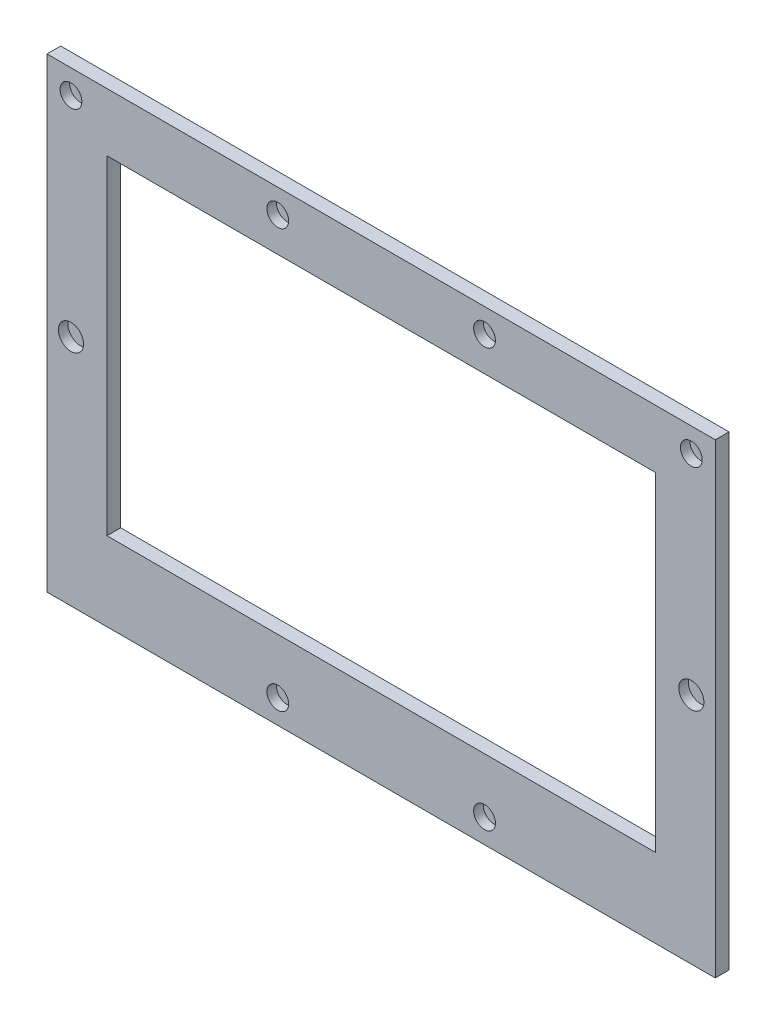
SolidWorks part; units mm, degrees
ref_plane "Front Plane" through (0, 0, 0) normal (0, 0, 1) x (1, 0, 0)
ref_plane "Top Plane" through (0, 0, 0) normal (0, 1, 0) x (1, 0, 0)
ref_plane "Right Plane" through (0, 0, 0) normal (1, 0, 0) x (0, 0, -1)
sketch "Sketch1" plane through (0, 0, 0) normal (0, 0, 1) x (1, 0, 0)
  line L1 (85.5, -56) -> (-85.5, -56)
  line L2 (85.5, -56) -> (85.5, 56)
  line L3 (85.5, 56) -> (-85.5, 56)
  line L4 (-85.5, -56) -> (-85.5, 56)
  line L5 (85.5, -56) -> (-85.5, 56) construction
  line L6 (85.5, 56) -> (-85.5, -56) construction
  line L11 (80, -45) -> (-80, -45)
  line L12 (80, -45) -> (80, 51)
  line L13 (80, 51) -> (-80, 51)
  line L14 (-80, -45) -> (-80, 51)
  line L15 (80, -45) -> (-80, 51) construction
  line L16 (80, 51) -> (-80, -45) construction
  line L17 (-14.5, -56) -> (14.5, -56)
  line L18 (-14.5, -56) -> (-14.5, -59)
  line L19 (-14.5, -59) -> (14.5, -59)
  line L20 (14.5, -56) -> (14.5, -59)
  line L21 (97.5, 68) -> (-97.5, 68)
  line L22 (97.5, 68) -> (97.5, -68)
  line L23 (97.5, -68) -> (-97.5, -68)
  line L24 (-97.5, 68) -> (-97.5, -68)
  line L25 (97.5, 68) -> (-97.5, -68) construction
  line L26 (97.5, -68) -> (-97.5, 68) construction
  point P0 (0, 0)
  point P6 (0, 0)
  point P7 (0, 3)
  point P16 (0, 0)
  dimension "D1" = 171
  dimension "D2" = 112
  dimension "D3" = 96
  dimension "D4" = 160
  dimension "D5" = 5
  dimension "D6" = 71
  dimension "D7" = 29
  dimension "D8" = 3
  dimension "D9" = 12
  dimension "D10" = 17.5
  dimension "D11" = 12
extrude "Boss-Extrude1" add sketch "Sketch1" against normal blind 2 contours L4 L1 L2 L3 L11 L14 L13 L12 | L21 L24 L23 L22 L1 L20 L19 L18 L4 L3 L2 | L20 L1 L18 L19 region at (50, -53.9559, 0) region at (0, -57.5, 0) region at (95.1226, 0, 0)
extrude "Boss-Extrude2" add sketch "Sketch1<3>" along normal blind 2 contours L21 L24 L23 L22 L1 L20 L19 L18 L4 L3 L2 | L4 L1 L2 L3 L11 L14 L13 L12 | L20 L1 L18 L19 region at (50, -53.9559, 0) region at (0, -57.5, 0) region at (95.1226, 0, 0)
sketch "Sketch1<3>" plane through (0, 0, 0) normal (0, 0, 1) x (1, 0, 0) same geometry as "Sketch1"
sketch "Sketch2" plane through (0, 0, 2) normal (0, 0, 1) x (1, 0, 0)
  line L0 (97.5, 68) -> (-97.5, 68) construction
  line L1 (90.5, -61) -> (-90.5, -61) construction
  line L2 (90.5, -61) -> (90.5, 61) construction
  line L3 (90.5, 61) -> (-90.5, 61) construction
  line L4 (-90.5, -61) -> (-90.5, 61) construction
  line L5 (90.5, -61) -> (-90.5, 61) construction
  line L6 (90.5, 61) -> (-90.5, -61) construction
  line L7 (-97.5, 68) -> (-97.5, -68) construction
  line L8 (-90.5, 61) -> (-30.1667, 61) construction
  line L9 (-30.1667, 61) -> (30.1667, 61) construction
  line L10 (30.1667, 61) -> (90.5, 61) construction
  line L11 (-90.5, 61) -> (-30.1667, 61) construction
  line L12 (-30.1667, 61) -> (30.1667, 61) construction
  line L13 (30.1667, 61) -> (90.5, 61) construction
  line L14 (90.5, 61) -> (90.5, 0) construction
  line L15 (90.5, 0) -> (90.5, -61) construction
  circle A0 centre (-90.5, 61) radius 3.175
  circle A2 centre (90.5, 61) radius 3.175
  circle A6 centre (-30.1667, -61) radius 3.175
  circle A7 centre (30.1667, -61) radius 3.175
  circle A8 centre (90.5, 0) radius 3.6737
  circle A9 centre (-30.1667, 61) radius 3.175
  circle A10 centre (30.1667, 61) radius 3.175
  circle A11 centre (-90.5, 0) radius 3.6737
  point P0 (0, 0)
  dimension "D1" = 6.35
  dimension "D2" = 7
  dimension "D3" = 7
extrude "Cut-Extrude1" cut sketch "Sketch2" against normal blind 2.794
